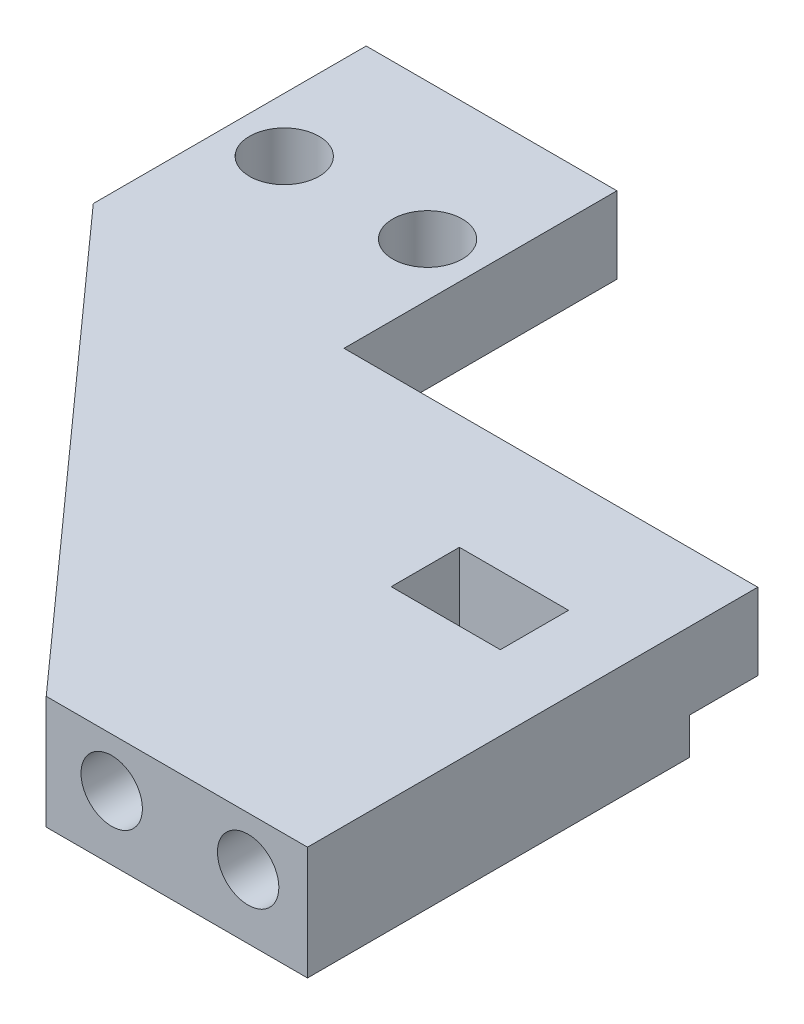
SolidWorks part; units mm, degrees
ref_plane "前视基准面" through (0, 0, 0) normal (0, 0, 1) x (1, 0, 0)
ref_plane "上视基准面" through (0, 0, 0) normal (0, 1, 0) x (1, 0, 0)
ref_plane "右视基准面" through (0, 0, 0) normal (1, 0, 0) x (0, 0, -1)
other "Configuration Table"
sketch "草图1" plane through (0, 0, 0) normal (0, 0, 1) x (1, 0, 0)
  line L1 (-11.1667, -5) -> (11.1667, -5)
  line L2 (-11.1667, -5) -> (-11.1667, 5)
  line L3 (-11.1667, 5) -> (11.1667, 5)
  line L4 (11.1667, -5) -> (11.1667, 5)
  line L5 (-11.1667, -5) -> (11.1667, 5) construction
  line L6 (-11.1667, 5) -> (11.1667, -5) construction
  point P0 (0, 0)
  dimension "D1" = 10
extrude "凸台-拉伸1" add sketch "草图1" along normal blind 30
sketch "草图2" plane through (0, -5, 0) normal (0, -1, 0) x (1, 0, 0)
  line L0 (-10.0833, 30.4566) -> (-10.0833, 0)
  line L1 (-10.0833, 30) -> (-10.0833, 38.1808) construction
  line L2 (-11.1667, 0) -> (11.1667, 0) construction
sketch "草图3" plane through (0, 0, 30) normal (0, 0, 1) x (1, 0, 0)
  line L0 (-9.2333, 0.05) -> (-9.2333, -5.0113)
  line L2 (9.4667, -5) -> (9.4667, 0.05)
  circle A0 centre (5.1167, -0.3) radius 2.25
  circle A1 centre (-4.8833, -0.3) radius 2.25
  arc A3 (9.4667, 0.05) -> (7.4667, 2.05) centre (7.4667, 0.05) ccw
  arc A4 (-9.2333, 0.05) -> (-6.4511, 1.8907) centre (-7.2333, 0.05) cw
sketch "草图4" plane through (0, -5, 0) normal (0, -1, 0) x (1, 0, 0)
  line L1 (-11.1667, 30) -> (-10.0833, 30)
  line L2 (-11.1667, 30) -> (-11.1667, 0)
  line L3 (-11.1667, 0) -> (-10.0833, 0)
  line L4 (-10.0833, 30) -> (-10.0833, 0)
extrude "切除-拉伸1" cut sketch "草图4" against normal blind 30
extrude "切除-拉伸2" cut sketch "草图3" against normal blind 15 contours A1 | A0 region at (-4.8833, -0.3, 30)
sketch "草图5" plane through (0, 0, 30) normal (0, 0, 1) x (1, 0, 0)
  line L0 (9.4667, -5) -> (9.4667, 0.05) construction
  line L1 (-9.2333, -5.0113) -> (9.4667, -5.0113)
  line L2 (-9.2333, -5.0113) -> (-9.2333, 3.3044)
  line L3 (-9.2333, 3.3044) -> (9.4667, 3.3044)
  line L4 (9.4667, -5.0113) -> (9.4667, 3.3044)
extrude "切除-拉伸3" cut sketch "草图5" against normal blind 30 flip side to cut
sketch "草图6" plane through (9.4667, 0, 0) normal (1, 0, 0) x (0, 0, -1)
  line L0 (22.3266, -2.313) -> (13.2059, -2.313) construction
sketch "草图7" plane through (0, 3.3044, 0) normal (0, 1, 0) x (1, 0, 0)
  arc A0 (-18.3547, 13) -> (-15.8066, 10.45) centre (-15.8066, 12.9981) cw
sketch "草图10" plane through (0, 0, 0) normal (0, 0, -1) x (-1, 0, 0)
  line L4 (-9.4667, -5) -> (9.2333, -5)
  line L5 (9.2333, -5) -> (9.2333, 3.3044)
  line L6 (9.2333, 3.3044) -> (-9.4667, 3.3044)
  line L7 (-9.4667, 3.3044) -> (-9.4667, -5)
  line L8 (-9.4667, -5) -> (9.2333, -5)
  line L9 (9.2333, -5) -> (9.2333, 3.3044)
  line L10 (9.2333, 3.3044) -> (-9.4667, 3.3044)
  line L11 (-9.4667, 3.3044) -> (-9.4667, -5)
  dimension "D1" = 0
extrude "凸台-拉伸2" add sketch "草图10" along normal blind 18
sketch "草图11" plane through (9.4667, 0, 0) normal (1, 0, 0) x (0, 0, -1)
  line L1 (18, -5) -> (-2, -5)
  line L2 (18, -5) -> (18, -2.313)
  line L3 (18, -2.313) -> (-2, -2.313)
  line L4 (-2, -5) -> (-2, -2.313)
  dimension "D1" = 20
extrude "切除-拉伸5" cut sketch "草图11" against normal through all
sketch "草图12" plane through (0, -2.313, 0) normal (0, -1, 0) x (1, 0, 0)
  line L0 (-9.2333, -12.9981) -> (9.4667, -12.9981)
  line L1 (-9.2333, -18) -> (-9.2333, 2) construction
  line L2 (9.4667, -200022.3266) -> (9.4667, 199986.7941) construction
  circle A0 centre (-4.7333, -12.9981) radius 2.5481
  circle A1 centre (4.9667, -12.9981) radius 2.5481
  point P5 (-4.7333, -12.9981)
  point P8 (4.9667, -12.9981)
  point P11 (0.1167, -12.9981)
  dimension "D1" = 4.5
  dimension "D2" = 4.5
extrude "切除-拉伸6" cut sketch "草图12" against normal through all contours L0 A0 | L0 A0 | L0 A1 | L0 A1 region at (-4.7333, -2.313, -11.9167) region at (4.9667, -2.313, -11.9167) region at (4.9667, -2.313, -14.0796) region at (-4.7333, -2.313, -14.0796)
sketch "草图13" plane through (0, 3.3044, 0) normal (0, 1, 0) x (1, 0, 0)
  line L0 (-9.2333, 18) -> (-9.2333, -30) construction
  line L1 (9.4667, 18) -> (-9.2333, 18)
  line L2 (9.4667, 18) -> (9.4667, 23)
  line L3 (9.4667, 23) -> (-9.2333, 23)
  line L4 (-9.2333, 18) -> (-9.2333, 23)
extrude "凸台-拉伸3" add sketch "草图13" against normal up to surface (5.6174 mm away) up to face at (-4.7333, -2.313, -15.5463)
sketch "草图14" plane through (0, 3.3044, 0) normal (0, 1, 0) x (1, 0, 0)
  line L1 (-4, -5.4) -> (4, -5.4)
  line L2 (-4, -5.4) -> (-4, -10.4)
  line L3 (-4, -10.4) -> (4, -10.4)
  line L4 (4, -5.4) -> (4, -10.4)
  dimension "D1" = 4
  dimension "D2" = 4
  dimension "D3" = 5.4
  dimension "D4" = 5
extrude "切除-拉伸7" cut sketch "草图14" against normal through all
sketch "草图15" plane through (0, 3.3044, 0) normal (0, 1, 0) x (1, 0, 0)
  line L0 (12.4664, 3) -> (12.4664, 23)
  line L1 (-17.5336, 1.8172) -> (-17.5336, 27.7399)
  point P4 (0, 0)
  point P5 (0, 0)
  dimension "D1" = 30
sketch "草图16" plane through (0, 3.3044, 0) normal (0, 1, 0) x (1, 0, 0)
  line L0 (-20.8565, 3) -> (-11.1516, 3)
sketch "草图17" plane through (0, 3.3044, 0) normal (0, 1, 0) x (1, 0, 0)
  line L0 (-20.8565, 3) -> (-11.1516, 3) construction
sketch "草图18" plane through (-9.2333, 0, 0) normal (-1, 0, 0) x (0, 0, 1)
  line L0 (-3, 3.3044) -> (-3, -2.313)
  line L1 (-3, 3.3044) -> (-23, 3.3044) construction
  line L2 (-23, -2.313) -> (2, -2.313) construction
  line L3 (-3, -2.313) -> (2, -2.313)
  line L4 (2, -2.313) -> (2, -5)
  line L5 (2, -5) -> (30, -5)
  line L6 (30, -5) -> (30, 3.3044)
  line L7 (30, 3.3044) -> (-3, 3.3044)
extrude "凸台-拉伸4" add sketch "草图18" along normal blind 30
sketch "草图19" plane through (0, 0, -3) normal (0, 0, -1) x (-1, 0, 0)
  line L0 (20.8565, 3.3044) -> (11.1516, 3.3044) construction
  line L1 (20.8565, 3.3044) -> (39.2333, 3.3044)
  line L2 (20.8565, 3.3044) -> (20.8565, -2.313)
  line L3 (20.8565, -2.313) -> (39.2333, -2.313)
  line L4 (39.2333, 3.3044) -> (39.2333, -2.313)
  line L5 (200020.8565, 3.3044) -> (-199988.8484, 3.3044) construction
extrude "凸台-拉伸5" add sketch "草图19" along normal up to surface (20 mm away) up to face at (0.1167, 0.4957, -23)
sketch "草图20" plane through (0, 3.3044, 0) normal (0, 1, 0) x (1, 0, 0)
  line L0 (-39.2333, -30) -> (-39.2333, 23) construction
  circle A0 centre (-35.2333, 12.9981) radius 2.5481
  circle A1 centre (-24.7333, 12.9981) radius 2.5481
  dimension "D1" = 4
  dimension "D2" = 14.5
extrude "切除-拉伸8" cut sketch "草图20" against normal blind 30
sketch "草图21" plane through (0, 3.3044, 0) normal (0, 1, 0) x (1, 0, 0)
  line L1 (-9.2333, 3) -> (9.4667, 3)
  line L2 (-9.2333, 3) -> (-9.2333, 23)
  line L3 (-9.2333, 23) -> (9.4667, 23)
  line L4 (9.4667, 3) -> (9.4667, 23)
extrude "切除-拉伸9" cut sketch "草图21" against normal blind 30
sketch "草图22" plane through (0, 3.3044, 0) normal (0, 1, 0) x (1, 0, 0)
  line L0 (-39.2333, 3) -> (-9.6813, -30)
  line L1 (-200020.8565, 3) -> (199988.8484, 3) construction
  line L2 (-39.2333, -30) -> (-39.2333, 23) construction
  line L3 (9.4667, -30) -> (-39.2333, -30) construction
  line L4 (-39.2333, 3) -> (-39.2333, -30)
  line L5 (-39.2333, -30) -> (-9.6813, -30)
extrude "切除-拉伸10" cut sketch "草图22" against normal blind 30
sketch "草图23" plane through (0, 0, 30) normal (0, 0, 1) x (1, 0, 0)
  line L1 (-34.7558, -2.313) -> (-9.6813, -2.313)
  line L2 (-34.7558, -2.313) -> (-34.7558, -5)
  line L3 (-34.7558, -5) -> (-9.6813, -5)
  line L4 (-9.6813, -2.313) -> (-9.6813, -5)
extrude "切除-拉伸11" cut sketch "草图23" against normal blind 30
sketch "草图26" plane through (-9.6813, 0, 0) normal (-1, 0, 0) x (0, 0, 1)
  line L0 (30, -2.313) -> (30, 3.3044) construction
  line L1 (-3, -2.313) -> (30, -2.313)
  line L2 (-3, -2.313) -> (-3, -1.503)
  line L3 (-3, -1.503) -> (30, -1.503)
  line L4 (30, -2.313) -> (30, -1.503)
  dimension "D1" = 0.81
extrude "切除-拉伸12" cut sketch "草图26" along normal blind 30
